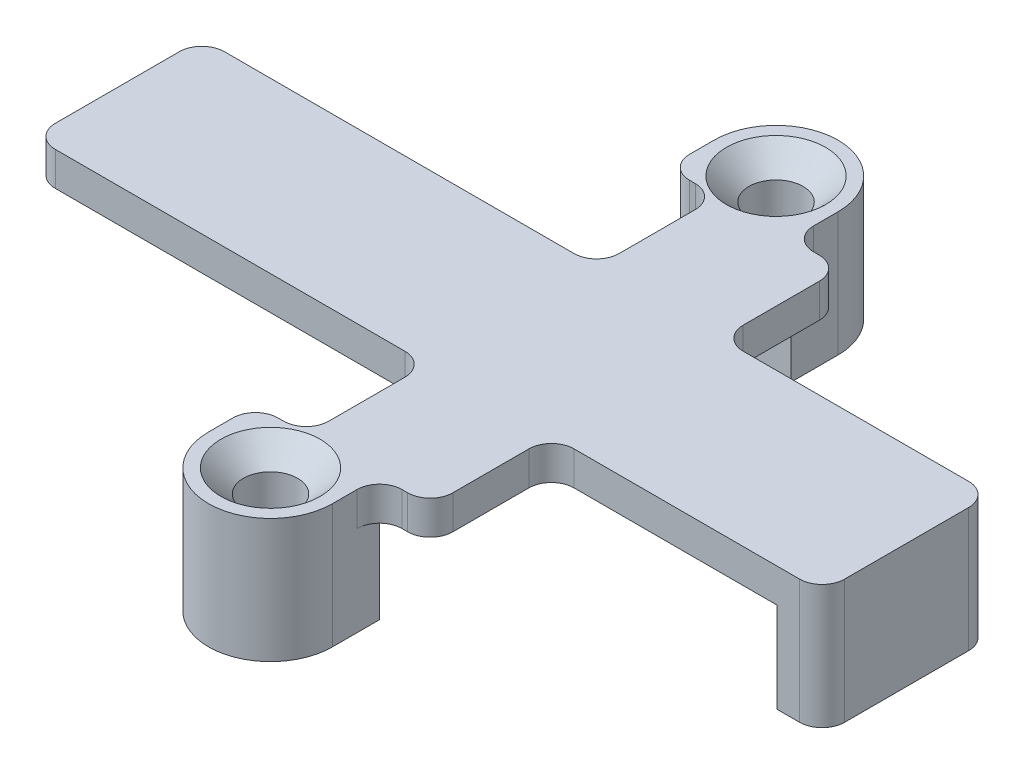
SolidWorks part; units mm, degrees
note: The reader was unsure of these and kept them because the rebuilt part matched: shared geometry of "Sketch1<4>".
ref_plane "Front Plane" through (0, 0, 0) normal (0, 0, 1) x (1, 0, 0)
ref_plane "Top Plane" through (0, 0, 0) normal (0, 1, 0) x (1, 0, 0)
ref_plane "Right Plane" through (0, 0, 0) normal (1, 0, 0) x (0, 0, -1)
sketch "Sketch1" plane through (0, 0, 0) normal (0, 1, 0) x (1, 0, 0)
  line L0 (0, 11.2072) -> (0, -11.2072) construction
  line L1 (0, 11.2072) -> (0, -11.2072) construction
  line L2 (2.75, 11.2072) -> (2.75, -11.2072)
  line L3 (-2.75, 11.2072) -> (-2.75, -11.2072)
  line L4 (15, 0) -> (-18, 0) construction
  line L5 (15, 3.75) -> (-18, 3.75)
  line L6 (15, 3.75) -> (15, -3.75)
  line L7 (15, -3.75) -> (-18, -3.75)
  line L8 (-18, 3.75) -> (-18, -3.75)
  line L9 (2.75, 9.125) -> (-2.75, 9.125)
  line L10 (15, 3.75) -> (17, 3.75)
  line L11 (15, 3.75) -> (15, -3.75)
  line L12 (15, -3.75) -> (17, -3.75)
  line L13 (17, 3.75) -> (17, -3.75)
  line L14 (15, 9) -> (-18, 9) construction
  line L15 (15, 9) -> (15, -9) construction
  line L16 (15, -9) -> (-18, -9) construction
  line L17 (-18, 9) -> (-18, -9) construction
  line L18 (2.75, -9.125) -> (-2.75, -9.125)
  line L19 (2.25, 9.125) -> (2.25, -9.125) construction
  line L20 (-0.5, 9.125) -> (5, 9.125)
  line L21 (-0.5, 9.125) -> (-0.5, -9.125)
  line L22 (-0.5, -9.125) -> (5, -9.125)
  line L23 (5, 9.125) -> (5, -9.125)
  arc A0 (2.75, 11.2072) -> (-2.75, 11.2072) centre (0, 11.2072) ccw
  arc A1 (-2.75, -11.2072) -> (2.75, -11.2072) centre (0, -11.2072) ccw
  circle A2 centre (0, 11.2072) radius 1.75
  circle A3 centre (0, -11.2072) radius 1.75
  point P2 (0, 0)
  point P4 (0, 0)
  point P25 (15, 0)
  dimension "D2" = 1
  dimension "D3" = 3.5
  dimension "D1" = 22.4144
  dimension "D4" = 15
  dimension "D5" = 7.5
  dimension "D6" = 33
  dimension "D7" = 2
  dimension "D8" = 18
  dimension "D9" = 0.125
  dimension "D10" = 5.5
  dimension "D11" = 12.75
extrude "Boss-Extrude1" add sketch "Sketch1" along normal blind 1.5 contours L5 L8 L7 L3 | L21 L5 L3 L7 | L5 L21 L7 L2 | L23 L5 L2 L7 | L7 L21 L18 L2 | L23 L7 L2 L22 | L5 L23 L7 L6 | L13 L10 L6 L12 | L23 L20 L2 L5 | L9 L21 L5 L2 | L2 A0 L3 L9 A2 | A2 | L3 A1 L2 L18 A3 | A3
extrude "Boss-Extrude2" add sketch "Sketch1<4>" against normal blind 4 contours L2 A0 L3 L9 A2 | L3 A1 L2 L18 A3 | L13 L10 L6 L12 | A2 | A3
sketch "Sketch1<4>" plane through (0, 0, 0) normal (0, 1, 0) x (1, 0, 0) same geometry as "Sketch1"
hole_wizard "CSK for M2 Flat Head Machine Screw1" positions "3DSketch1" profile "Sketch2" countersink size "M2" standard "ANSI Metric" end condition through all
sketch3d "3DSketch1"
  circle A0 centre (0, 0, 11.2072) radius 1.75 construction
  circle A1 centre (0, 0, -11.2072) radius 1.75 construction
  point P0 (0, 0, -11.2072)
  point P3 (0, 0, 11.2072)
  point P6 (0, 1.5, -11.2072)
  point P8 (0, 1.5, 11.2072)
  point P14 (0, 1.75, 11.2072)
  point P18 (0, 1.75, -11.2072)
sketch "Sketch2" plane through (0, 1.5, 11.2072) normal (1, 0, 0) x (0, 0, 1)
  line L0 (0, 0) -> (0, 5.5)
  line L1 (0, 5.5) -> (1.2, 5.5)
  line L2 (1.2, 5.5) -> (1.2, 1)
  line L3 (1.2, 1) -> (2.2, 0)
  line L5 (2.2, 0) -> (0, 0)
  line L6 (-1.2, 1) -> (-2.2, 0) construction
  line L11 (0, -6.35) -> (0, 107.95) construction
  dimension "Thru Hole Dia." = 2.4
  dimension "Thru Hole Depth" = 5.5
  dimension "Near C'Sink Dia." = 4.4
  dimension "Near C'Sink Angle" = 90
fillet "Fillet1" radius 1 20 edges at (-0.5, 0.7207, 9.125) (-0.5, 0.7207, -9.125) (-0.5, 0.75, 3.75) (-18, 0.75, 3.75) (-18, 0.75, -3.75) (-0.5, 0.75, -3.75) (-2.75, -1.25, -9.125) (2.75, 0.75, -9.125) (5, 0.75, -9.125) (5, 0.75, -3.75) (17, -1.25, -3.75) (17, -1.25, 3.75) (5, 0.75, 3.75) (5, 0.75, 9.125) (2.75, 0.75, 9.125) (-2.75, -1.25, 9.125)
move or copy body "Body-Move/Copy1" bodies to move or copy 104
